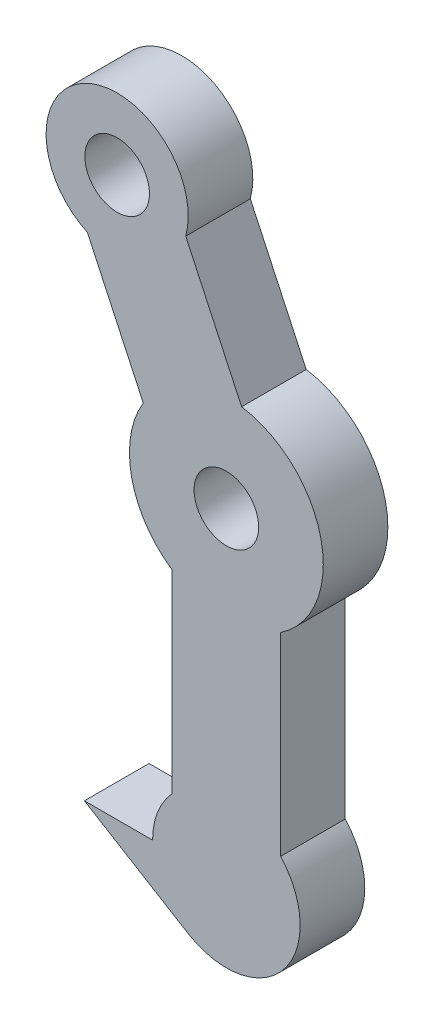
SolidWorks part; units mm, degrees
ref_plane "Front Plane" through (0, 0, 0) normal (0, 0, 1) x (1, 0, 0)
ref_plane "Top Plane" through (0, 0, 0) normal (0, 1, 0) x (1, 0, 0)
ref_plane "Right Plane" through (0, 0, 0) normal (1, 0, 0) x (0, 0, -1)
sketch "Sketch1" plane through (0, 0, 0) normal (0, 0, 1) x (1, 0, 0)
  line L0 (1.4992, 9.4063) -> (-3.9943, 21.1872)
  line L1 (-8.1693, 4.8978) -> (-13.6628, 16.6787)
  line L2 (-5.334, -7.8914) -> (-5.334, -26.9414)
  line L3 (5.334, -7.8914) -> (5.334, -26.9414)
  line L4 (0, 0) -> (-10.7345, 23.0202) construction
  line L5 (-7.2533, -31.8566) -> (-13.9514, -31.8566)
  line L6 (-13.9514, -31.8566) -> (-3.771, -38.0526)
  line L7 (0, -31.8566) -> (0, 0) construction
  arc A0 (5.334, -7.8914) -> (1.4992, 9.4063) centre (0, 0) ccw
  circle A1 centre (-10.7345, 23.0202) radius 3.175
  arc A2 (-3.771, -38.0526) -> (5.334, -26.9414) centre (0, -31.8566) ccw
  arc A3 (-3.9943, 21.1872) -> (-13.6628, 16.6787) centre (-10.7345, 23.0202) ccw
  circle A4 centre (0, 0) radius 3.175
  arc A5 (-5.334, -26.9414) -> (-7.2533, -31.8566) centre (0, -31.8566) ccw
  arc A6 (-8.1693, 4.8978) -> (-5.334, -7.8914) centre (0, 0) ccw
  dimension "D1" = 6.35
  dimension "D3" = 6.35
  dimension "D4" = 19.05
  dimension "D5" = 13.97
  dimension "D2" = 155
  dimension "D6" = 10.668
  dimension "D7" = 10.668
  dimension "D8" = 25.4
  dimension "D9" = 19.05
extrude "Boss-Extrude1" add sketch "Sketch1" along normal mid plane 6.35
